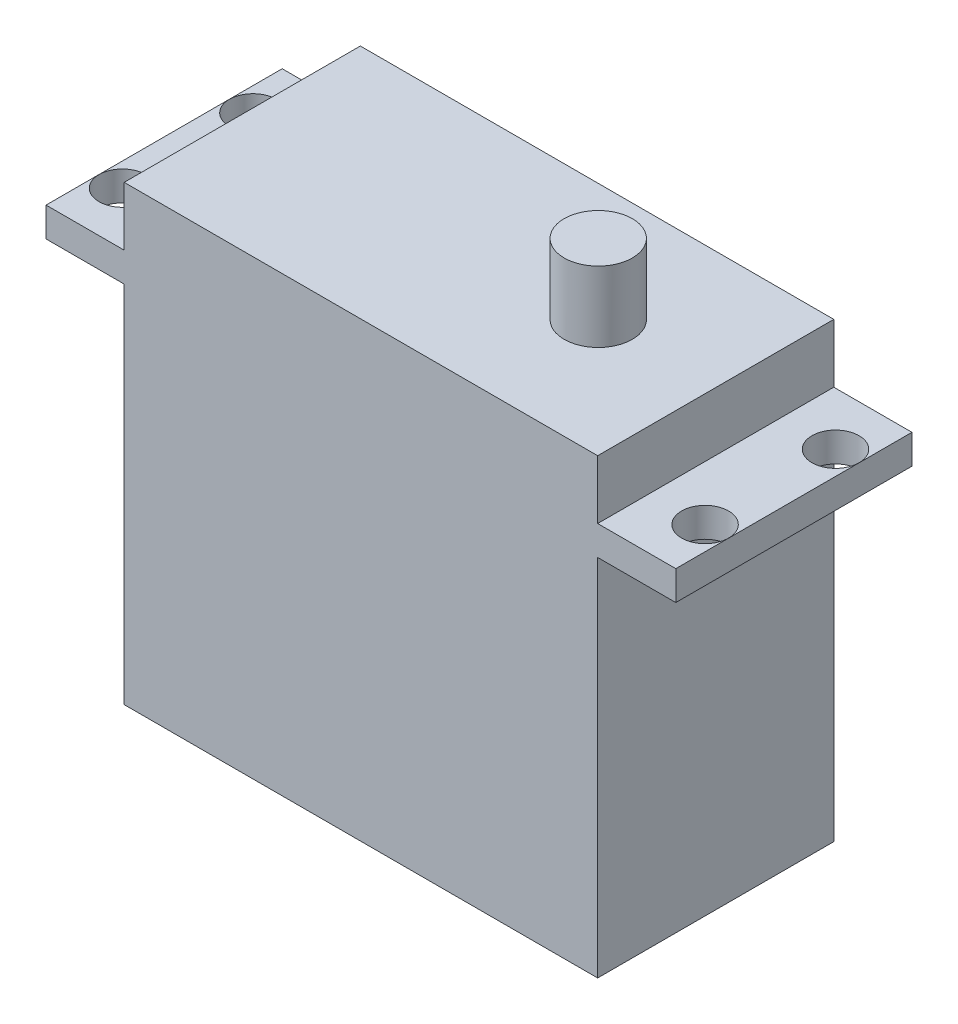
SolidWorks part; units mm, degrees
ref_plane "Front Plane" through (0, 0, 0) normal (0, 0, 1) x (1, 0, 0)
ref_plane "Top Plane" through (0, 0, 0) normal (0, 1, 0) x (1, 0, 0)
ref_plane "Right Plane" through (0, 0, 0) normal (1, 0, 0) x (0, 0, -1)
sketch "Sketch1" plane through (0, 0, 0) normal (0, 1, 0) x (1, 0, 0)
  line L1 (-20.15, -10.05) -> (20.15, -10.05)
  line L2 (-20.15, -10.05) -> (-20.15, 10.05)
  line L3 (-20.15, 10.05) -> (20.15, 10.05)
  line L4 (20.15, -10.05) -> (20.15, 10.05)
  line L5 (-20.15, -10.05) -> (20.15, 10.05) construction
  line L6 (-20.15, 10.05) -> (20.15, -10.05) construction
  point P0 (0, 0)
  dimension "D1" = 20.1
  dimension "D2" = 40.3
extrude "Boss-Extrude1" add sketch "Sketch1" along normal blind 38.5
sketch "Sketch2" plane through (0, 38.5, 0) normal (0, 1, 0) x (1, 0, 0)
  line L0 (20.15, 0) -> (10.15, 0) construction
  line L1 (20.15, -10.05) -> (20.15, 10.05) construction
  circle A0 centre (10.15, 0) radius 2.9
  dimension "D2" = 5.8
  dimension "D1" = 10
extrude "Boss-Extrude2" add sketch "Sketch2" along normal blind 6
sketch "Sketch3" plane through (0, 38.5, 0) normal (0, 1, 0) x (1, 0, 0)
  line L0 (-26.8, 0) -> (26.8, 0) construction
  line L1 (-20.15, 10.05) -> (-26.8, 10.05)
  line L2 (-20.15, -10.05) -> (-26.8, -10.05)
  line L3 (-26.8, -10.05) -> (-26.8, 10.05)
  line L4 (20.15, 10.05) -> (26.8, 10.05)
  line L5 (26.8, 10.05) -> (26.8, -10.05)
  line L6 (26.8, -10.05) -> (20.15, -10.05)
  line L7 (-20.15, 10.05) -> (-20.15, -10.05)
  line L8 (20.15, 10.05) -> (20.15, -10.05)
  line L9 (-26.8, 3.75) -> (-26.8, -3.75)
  line L10 (0, -10.05) -> (0, 10.05) construction
  line L11 (-20.15, -10.05) -> (20.15, -10.05) construction
  line L12 (20.15, 10.05) -> (-20.15, 10.05) construction
  circle A0 centre (-24.7944, 5.55) radius 2
  circle A1 centre (-24.7944, -5.55) radius 2
  circle A2 centre (24.7944, -5.55) radius 2
  circle A3 centre (24.7944, 5.55) radius 2
  point P4 (0, 0)
  point P20 (-26.8, 0)
  line M4 (20.15, -10.05) -> (20.15, 10.05)
  line M6 (-20.15, 10.05) -> (-20.15, -10.05)
  dimension "D4" = 4
  dimension "D5" = 4.5
  dimension "D1" = 53.6
  dimension "D2" = 6.65
  dimension "D3" = 7.5
extrude "Boss-Extrude3" add sketch "Sketch3" against normal blind 2.5 from offset 5 contours L3 L2 L1 A0 A1 M6 | L6 L5 L4 A2 A3 M4 region at (-23.1695, 38.5, 0) region at (23.1695, 38.5, 0) offset against normal yes
